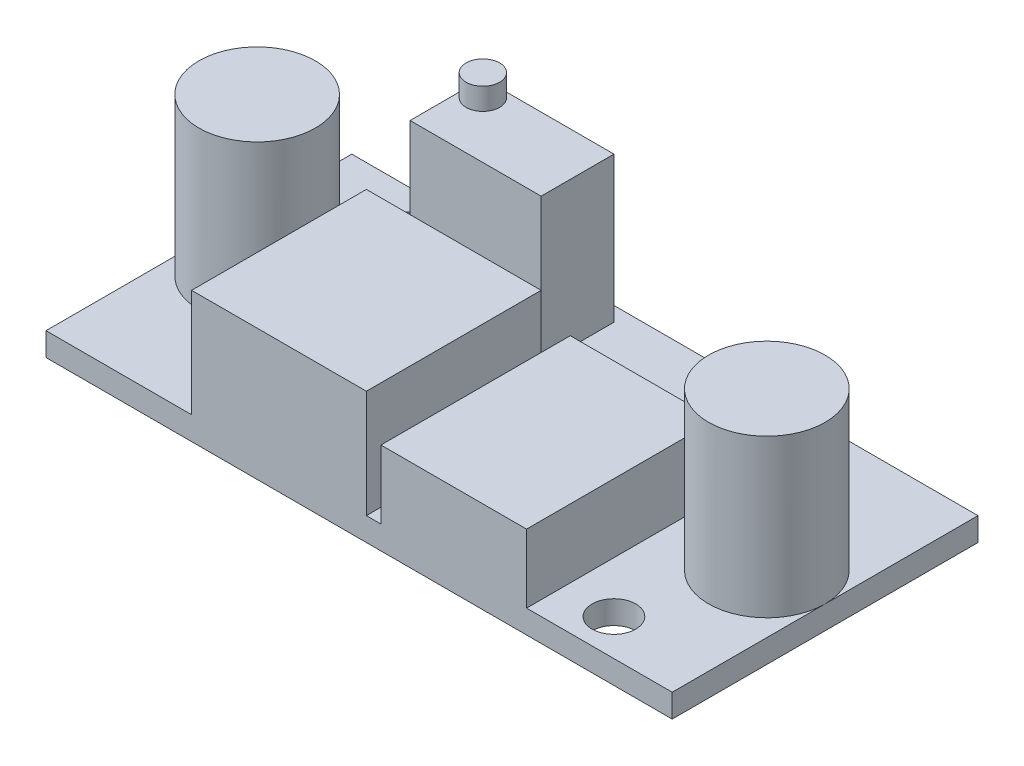
SolidWorks part; units mm, degrees
ref_plane "Front" through (0, 0, 0) normal (0, 0, 1) x (1, 0, 0)
ref_plane "Top" through (0, 0, 0) normal (0, 1, 0) x (1, 0, 0)
ref_plane "Right" through (0, 0, 0) normal (1, 0, 0) x (0, 0, -1)
sketch "Эскиз1" plane through (0, 0, 0) normal (0, 1, 0) x (1, 0, 0)
  line L1 (-21.5, 10.5) -> (21.5, 10.5)
  line L2 (-21.5, 10.5) -> (-21.5, -10.5)
  line L3 (-21.5, -10.5) -> (21.5, -10.5)
  line L4 (21.5, 10.5) -> (21.5, -10.5)
  line L5 (-21.5, 10.5) -> (21.5, -10.5) construction
  line L6 (-21.5, -10.5) -> (21.5, 10.5) construction
  point P0 (0, 0)
  dimension "D1" = 21
  dimension "D2" = 43
extrude "Бобышка-Вытянуть1" add sketch "Эскиз1" along normal blind 1.6
sketch "Эскиз2" plane through (0, 1.6, 0) normal (0, 1, 0) x (1, 0, 0)
  line L0 (0, 10.5) -> (0, -10.5) construction
  line L1 (21.5, 10.5) -> (-21.5, 10.5) construction
  line L2 (-21.5, -10.5) -> (21.5, -10.5) construction
  line L3 (-21.5, 10.5) -> (-21.5, -10.5) construction
  line L4 (-21.5, 0) -> (21.5, 0) construction
  line L6 (21.5, -10.5) -> (21.5, 10.5) construction
  line L7 (-11.5, -10.5) -> (0.5, -10.5)
  line L8 (-11.5, -10.5) -> (-11.5, 1.5)
  line L9 (-11.5, 1.5) -> (0.5, 1.5)
  line L10 (0.5, -10.5) -> (0.5, 1.5)
  line L11 (-11.5, 9.5) -> (-2.5, 9.5)
  line L12 (-11.5, 9.5) -> (-11.5, 4.5)
  line L13 (-11.5, 4.5) -> (-2.5, 4.5)
  line L14 (-2.5, 9.5) -> (-2.5, 4.5)
  line L15 (1.5, -10.5) -> (11.5, -10.5)
  line L16 (1.5, -10.5) -> (1.5, 2.5)
  line L17 (1.5, 2.5) -> (11.5, 2.5)
  line L18 (11.5, -10.5) -> (11.5, 2.5)
  circle A0 centre (-15, 8) radius 1.5
  circle A1 centre (15, -8) radius 1.5
  circle A2 centre (-17.5, 0) radius 4
  circle A3 centre (17.5, 0) radius 4
  point P14 (-21.5, 0)
  line M16 (-21.5, -10.5) -> (21.5, -10.5)
  dimension "D1" = 8
  dimension "D2" = 3
  dimension "D3" = 2.5
  dimension "D4" = 2.5
  dimension "D5" = 6.5
  dimension "D6" = 6.5
  dimension "D7" = 12
  dimension "D8" = 10
  dimension "D9" = 1
  dimension "D10" = 13
  dimension "D11" = 10
  dimension "D12" = 1
  dimension "D13" = 10
  dimension "D14" = 9
  dimension "D15" = 5
extrude "Вырез-Вытянуть1" cut sketch "Эскиз2" against normal through all contours A0 | A1 region at (-15, 1.6, -8) region at (15, 1.6, 8)
extrude "Бобышка-Вытянуть2" add sketch "Эскиз2<3>" along normal blind 10.8 contours A2 | A3 region at (-17.5, 1.6, 0) region at (17.5, 1.6, 0)
sketch "Эскиз2<3>" plane through (0, 1.6, 0) normal (0, 1, 0) x (1, 0, 0) same geometry as "Эскиз2"
extrude "Бобышка-Вытянуть3" add sketch "Эскиз2<4>" along normal blind 7.4 contours L10 L9 L8 M16 region at (-5.5, 1.6, 4.5)
sketch "Эскиз2<4>" plane through (0, 1.6, 0) normal (0, 1, 0) x (1, 0, 0) same geometry as "Эскиз2"
extrude "Бобышка-Вытянуть4" add sketch "Эскиз2<5>" along normal blind 4.7 contours L18 L17 L16 M16 region at (6.5, 1.6, 4)
sketch "Эскиз2<5>" plane through (0, 1.6, 0) normal (0, 1, 0) x (1, 0, 0) same geometry as "Эскиз2"
extrude "Бобышка-Вытянуть5" add sketch "Эскиз2<6>" along normal blind 10 contours L14 L11 L12 L13 region at (-7, 1.6, -7)
sketch "Эскиз2<6>" plane through (0, 1.6, 0) normal (0, 1, 0) x (1, 0, 0) same geometry as "Эскиз2"
sketch "Эскиз3" plane through (0, 11.6, 0) normal (0, 1, 0) x (1, 0, 0)
  line L0 (-11.5, 9.5) -> (-2.5, 9.5) construction
  line L1 (-11.5, 9.5) -> (-11.5, 4.5) construction
  circle A0 centre (-10.35, 8.35) radius 1.15
  point P2 (-10.35, 9.5)
  point P3 (-11.5, 8.35)
  dimension "D1" = 2.3
extrude "Бобышка-Вытянуть6" add sketch "Эскиз3" along normal blind 1.5
